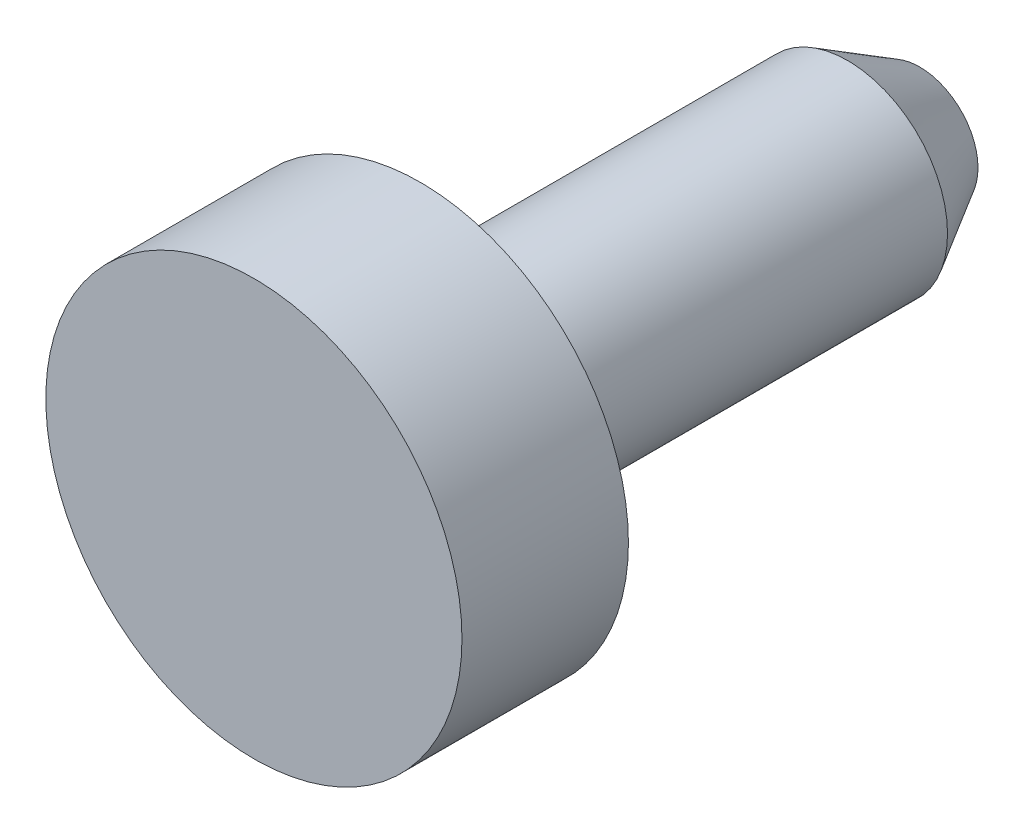
SolidWorks part; units mm, degrees
ref_plane "Alzado" through (0, 0, 0) normal (0, 0, 1) x (1, 0, 0)
ref_plane "Planta" through (0, 0, 0) normal (0, 1, 0) x (1, 0, 0)
ref_plane "Vista lateral" through (0, 0, 0) normal (1, 0, 0) x (0, 0, -1)
sketch "Croquis1" plane through (0, 0, 0) normal (0, 0, 1) x (1, 0, 0)
  circle A0 centre (0, 0) radius 2.5
  dimension "D1" = 5
extrude "Saliente-Extruir1" add sketch "Croquis1" along normal blind 2
sketch "Croquis2" plane through (0, 0, 0) normal (0, 0, 1) x (1, 0, 0)
  circle A0 centre (0, 0) radius 1.2
  dimension "D1" = 2.4
extrude "Saliente-Extruir2" add sketch "Croquis2" against normal blind 6
chamfer "Chaflán1" distance 0.5 angle 60 1 edges at (1.2, 0, -6) first distance on face at (1.2, 0, -6)
